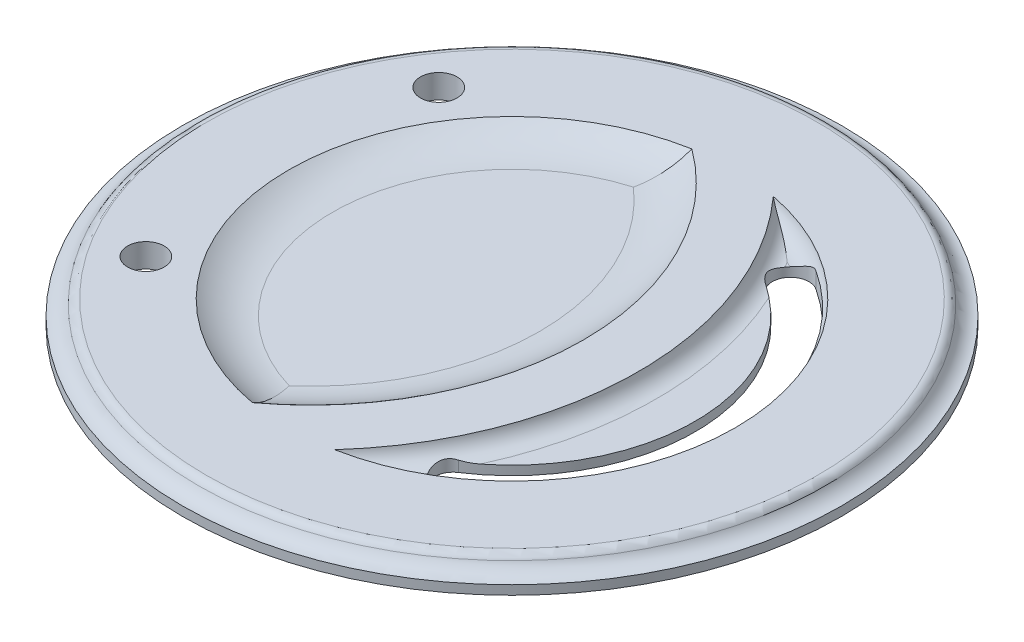
SolidWorks part; units mm, degrees
ref_plane "Front Plane" through (0, 0, 0) normal (0, 0, 1) x (1, 0, 0)
ref_plane "Top Plane" through (0, 0, 0) normal (0, 1, 0) x (1, 0, 0)
ref_plane "Right Plane" through (0, 0, 0) normal (1, 0, 0) x (0, 0, -1)
sketch "Sketch1" plane through (0, 0, 0) normal (0, 1, 0) x (1, 0, 0)
  line L0 (0, 0) -> (-122.0849, 0) construction
  line L1 (-38.1, 0) -> (-38.1, 25.4) construction
  line L2 (0, 0) -> (38.1, 0) construction
  line L3 (38.1, 0) -> (19.05, -29.2721) construction
  circle A0 centre (0, 0) radius 57.15
  circle A2 centre (-38.1, 25.4) radius 3.175
  circle A3 centre (-38.1, -25.4) radius 3.175
  arc A4 (17.3182, -26.611) -> (17.3182, 26.611) centre (0, 0) ccw
  arc A5 (20.7818, -31.9331) -> (20.7818, 31.9331) centre (0, 0) ccw
  circle A6 centre (0, 0) radius 34.925 construction
  arc A7 (17.3182, -26.611) -> (20.7818, -31.9331) centre (19.05, -29.2721) ccw
  arc A8 (20.7818, -31.9331) -> (21.6296, -27.4211) centre (19.05, -29.2721) ccw construction
  arc A9 (21.6296, -27.4211) -> (20.7818, -26.611) centre (19.05, -29.2721) ccw construction
  arc A10 (20.7818, -26.611) -> (17.3182, -26.611) centre (19.05, -29.2721) ccw construction
  arc A11 (17.3182, 26.611) -> (20.7818, 31.9331) centre (19.05, 29.2721) cw
  arc A12 (-31.75, 0) -> (17.3182, -26.611) centre (0, 0) ccw construction
  circle A13 centre (0, 0) radius 31.75 construction
  arc A14 (-38.1, 0) -> (20.7818, -31.9331) centre (0, 0) ccw construction
  circle A15 centre (0, 0) radius 38.1 construction
  arc A16 (17.3182, 26.611) -> (-31.75, 0) centre (0, 0) ccw construction
  arc A17 (20.7818, 31.9331) -> (-38.1, 0) centre (0, 0) ccw construction
  dimension "D1" = 114.3
  dimension "D4" = 6.35
  dimension "D2" = 50.8
  dimension "D3" = 38.1
  dimension "D6" = 6.35
extrude "MainPlate" add sketch "Sketch1" along normal blind 1.5875
sketch "Sketch3" plane through (0, 1.5875, 0) normal (0, 1, 0) x (1, 0, 0)
  line L0 (0, 0) -> (-38.735, 0) construction
  circle A1 centre (0, 0) radius 38.735
  circle A2 centre (0, 0) radius 54.61
  circle A3 centre (0, 0) radius 54.61
  circle A4 centre (-34.8945, 0) radius 47.2762
  circle A5 centre (-34.8945, 0) radius 56.8012
  circle M4 centre (-38.1, 25.4) radius 3.175
  circle M6 centre (-38.1, -25.4) radius 3.175
  dimension "D1" = 2.54
  dimension "D2" = 15.875
  dimension "D3" = 9.525
extrude "ReinforcementRib" add sketch "Sketch3" along normal blind 2.54 contours A5 A3 A1 | A1 A5 A4 | A3 A5 A1 A4 | A1 A5 A3 A4 | A3 A4 A1 M6 M4
fillet "Fillet1" radius 12.7 2 edges at (12.3817, 1.5875, 0) (-38.735, 1.5875, 0)
fillet "Fillet4" radius 1.5875 1 edges at (0, 4.1275, 54.61)
fillet "Fillet5" radius 3.175 1 edges at (0, 1.5875, 54.61)
fillet "Fillet6" radius 3.175 1 edges at (21.9067, 1.5875, 0)
fillet "Fillet7" radius 3.175 1 edges at (38.735, 1.5875, 0)
